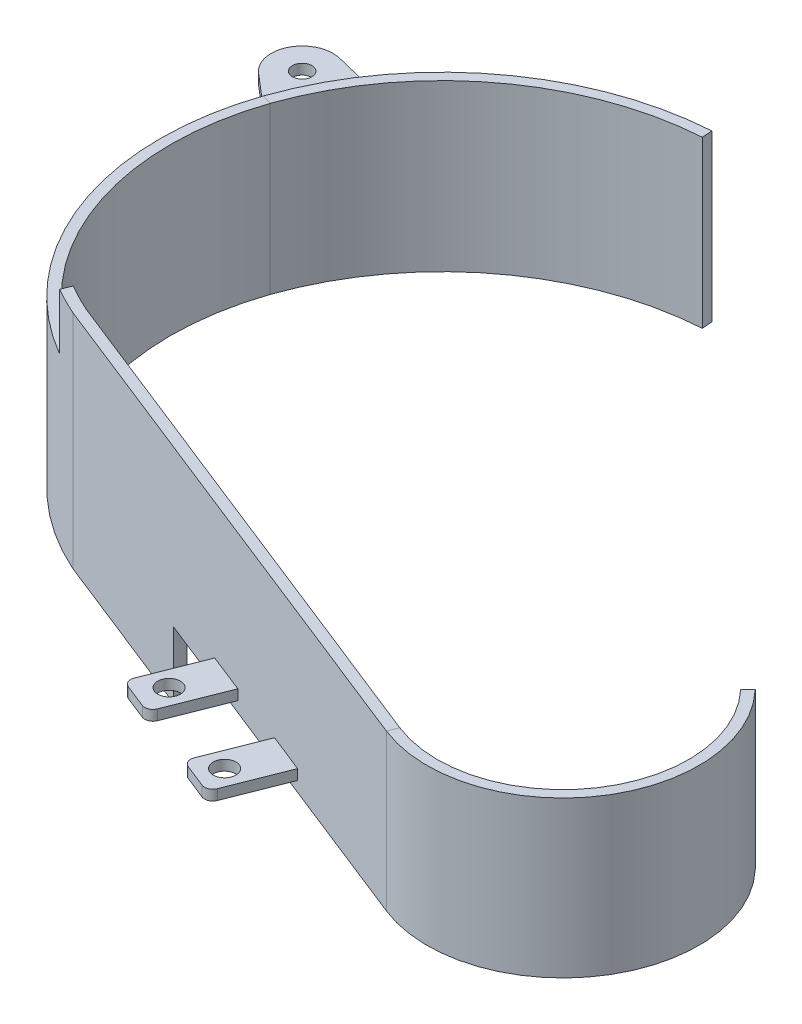
SolidWorks part; units mm, degrees
material "Alloy Steel"
ref_plane "X-Y Datum" through (0, 0, 0) normal (0, 0, 1) x (1, 0, 0)
ref_plane "X-Z Datum" through (0, 0, 0) normal (0, 1, 0) x (1, 0, 0)
ref_plane "Y-Z Datum" through (0, 0, 0) normal (1, 0, 0) x (0, 0, -1)
sketch "Sketch1" plane through (0, 0, 0) normal (0, 1, 0) x (1, 0, 0)
  line L0 (123.382, -46.1795) -> (82.7282, 60.9521) construction
  line L5 (80.7697, -109.5243) -> (-79.1962, -46.1795)
  line L6 (79.6008, -112.4763) -> (-80.422, -49.109)
  line L7 (123.0779, -46.7799) -> (125.3764, -44.5896)
  line L8 (-47.6198, 112.0697) -> (-47.8229, 115.2382)
  circle A0 centre (-42.1273, 26.3928) radius 85.8527 construction
  circle A1 centre (95.0328, -73.5055) radius 38.74 construction
  circle A2 centre (-7.1811, -92.7179) radius 3.5 construction
  circle A3 centre (22.9767, -105.7566) radius 3.5 construction
  circle A4 centre (-130.7728, 71.8939) radius 3 construction
  circle A5 centre (112.1618, -33.1147) radius 3.3 construction
  arc A6 (123.0779, -46.7799) -> (80.7697, -109.5243) centre (95.0328, -73.5055) cw
  arc A12 (-79.1962, -46.1795) -> (-123.2617, 54.4625) centre (-46.352, 28.169) cw
  arc A13 (-47.8229, 115.2382) -> (-126.2641, 55.4951) centre (-42.1273, 26.3928) ccw
  arc A14 (-80.422, -49.109) -> (-126.2641, 55.4951) centre (-46.352, 28.169) cw
  arc A15 (125.3764, -44.5896) -> (79.6008, -112.4763) centre (95.0328, -73.5055) cw
  arc A16 (-47.6198, 112.0697) -> (-123.2617, 54.4625) centre (-42.1273, 26.3928) ccw
  point P21 (-81.3964, -41.8997)
  point P34 (-78.7078, -46.7799)
  point P35 (-79.5053, -46.7799)
  point P37 (-79.1962, -46.7799)
  dimension "D1" = 6
  dimension "D2" = 171.7054
  dimension "D3" = 6.6
  dimension "D4" = 77.48
  dimension "D5" = 7
  dimension "D22" = 3.175
  dimension "D23" = 17.4234
  dimension "D6" = 22.9767
  dimension "D7" = 82.7282
  dimension "D8" = 95.0328
  dimension "D9" = 112.1618
  dimension "D10" = 123.382
  dimension "D11" = 7.1811
  dimension "D12" = 42.1273
  dimension "D13" = 130.7728
  dimension "D14" = 26.3928
  dimension "D15" = 60.9521
  dimension "D16" = 71.8939
  dimension "D17" = 33.1147
  dimension "D18" = 46.1795
  dimension "D19" = 73.5055
  dimension "D20" = 92.7179
  dimension "D21" = 105.7566
  dimension "D27" = 85.5529
  dimension "D28" = 17.4314
base flange "Base-Flange2" sketch "Sketch1" thickness 63.5 reverse thickness direction no parameters "D1"=0.7366
sketch "Sketch8" plane through (-27.712, 0, 69.9816) normal (-0.3682, 0, 0.9298) x (0.9298, 0, 0.3682)
  line L0 (36.9674, 0) -> (-134.738, 0) construction
  line L1 (-152.1442, -15.4686) -> (179.8218, -15.4686)
  line L2 (-152.1442, -15.4686) -> (-152.1442, 15.4686)
  line L3 (-152.1442, 15.4686) -> (179.8218, 15.4686)
  line L4 (179.8218, -15.4686) -> (179.8218, 15.4686)
  line L5 (-152.1442, -15.4686) -> (179.8218, 15.4686) construction
  line L6 (-152.1442, 15.4686) -> (179.8218, -15.4686) construction
  point P0 (13.8388, 0)
  dimension "D1" = 30.9372
extrude "Cut-Extrude1" cut sketch "Sketch8" against normal through all contours L2 L1 L4 L3 normal cut yes
sketch "Sketch9" plane through (-27.712, 0, 69.9816) normal (-0.3682, 0, 0.9298) x (0.9298, 0, 0.3682)
  line L0 (-56.6923, -15.4686) -> (-137.8267, -15.4686) construction
  line L1 (-215.9911, -32.8081) -> (-65.9363, -32.8081)
  line L2 (-215.9911, -32.8081) -> (-215.9911, 1.8709)
  line L3 (-215.9911, 1.8709) -> (-65.9363, 1.8709)
  line L4 (-65.9363, -32.8081) -> (-65.9363, 1.8709)
  line L5 (-215.9911, -32.8081) -> (-65.9363, 1.8709) construction
  line L6 (-215.9911, 1.8709) -> (-65.9363, -32.8081) construction
  point P0 (-140.9637, -15.4686)
  dimension "D1" = 34.679
extrude "Cut-Extrude2" cut sketch "Sketch9" against normal through all normal cut yes
sketch "Sketch11" plane through (0, -63.5, 0) normal (0, -1, 0) x (1, 0, 0)
  line L0 (-47.6198, -112.0697) -> (-47.8229, -115.2382) construction
  line L1 (-47.6198, -112.0697) -> (-47.8229, -115.2382)
  line L3 (-80.422, 49.109) -> (-29.0097, 69.4677)
  line L4 (-80.422, 49.109) -> (79.6008, 112.4763) construction
  line L5 (-29.0097, 69.4677) -> (-27.8408, 66.5157)
  line L6 (80.7697, 109.5243) -> (-79.1962, 46.1795) construction
  line L7 (-27.8408, 66.5157) -> (-79.1962, 46.1795)
  arc A0 (-79.1962, 46.1795) -> (-123.2617, -54.4625) centre (-46.352, -28.169) ccw construction
  arc A1 (-80.422, 49.109) -> (-126.2641, -55.4951) centre (-46.352, -28.169) ccw construction
  arc A2 (-126.2641, -55.4951) -> (-47.8229, -115.2382) centre (-42.1273, -26.3928) ccw construction
  arc A3 (-123.2617, -54.4625) -> (-47.6198, -112.0697) centre (-42.1273, -26.3928) ccw construction
  arc A4 (-79.1962, 46.1795) -> (-123.2617, -54.4625) centre (-46.352, -28.169) ccw
  arc A5 (-80.422, 49.109) -> (-126.2641, -55.4951) centre (-46.352, -28.169) ccw
  arc A6 (-126.2641, -55.4951) -> (-47.8229, -115.2382) centre (-42.1273, -26.3928) ccw
  arc A7 (-123.2617, -54.4625) -> (-47.6198, -112.0697) centre (-42.1273, -26.3928) ccw
  point P7 (-27.8408, 69.4677)
extrude "Boss-Extrude1" add sketch "Sketch11" along normal blind 20.32 contours A4 A7 L1 A6 A5 L3 L5 L7
sketch "Sketch12" plane through (-27.712, 0, 69.9816) normal (-0.3682, 0, 0.9298) x (0.9298, 0, 0.3682)
  line L0 (60.2996, -15.4686) -> (60.2996, -50015.4686) construction
  line L3 (27.4596, -15.4686) -> (27.4596, -50015.4686) construction
  line L6 (27.4596, -63.5) -> (60.2996, -63.5) construction
  line L11 (21.1096, -60.2996) -> (33.8096, -60.2996)
  line L12 (21.1096, -60.2996) -> (21.1096, -57.1246)
  line L13 (21.1096, -57.1246) -> (33.8096, -57.1246)
  line L14 (33.8096, -60.2996) -> (33.8096, -57.1246)
  line L15 (21.1096, -60.2996) -> (33.8096, -57.1246) construction
  line L16 (21.1096, -57.1246) -> (33.8096, -60.2996) construction
  line L17 (-1.3958, -63.5) -> (115.4202, -63.5) construction
  line L18 (43.8796, -63.5) -> (43.8796, -15.4686) construction
  line L19 (-56.6923, -15.4686) -> (115.4202, -15.4686) construction
  line L20 (66.6496, -57.1246) -> (53.9496, -57.1246)
  line L21 (53.9496, -60.2996) -> (53.9496, -57.1246)
  line L22 (66.6496, -60.2996) -> (53.9496, -60.2996)
  line L23 (66.6496, -60.2996) -> (66.6496, -57.1246)
  circle A0 centre (27.4596, -58.7121) radius 3.3 construction
  point P4 (27.4596, -52.269)
  dimension "D1" = 6.6
  dimension "D2" = 3.2004
  dimension "D3" = 3.175
  dimension "D4" = 12.7
extrude "Boss-Extrude2" add sketch "Sketch12" along normal blind 21.59
sketch "Sketch13" plane through (0, -57.1246, 0) normal (0, 1, 0) x (1, 0, 0)
  circle A0 centre (22.9767, -105.7566) radius 3.5 construction
  circle A1 centre (-7.1811, -92.7179) radius 3.5 construction
  circle A2 centre (22.9767, -105.7566) radius 3.5
  circle A3 centre (-7.1811, -92.7179) radius 3.5
extrude "Cut-Extrude5" cut sketch "Sketch13" against normal blind 21.59 normal cut yes
fillet "Fillet1" radius 2.54 4 edges at (-16.034, -58.7121, 97.8271) (-4.2261, -58.7121, 102.5029) (14.4992, -58.7121, 109.9179) (26.3071, -58.7121, 114.5937)
ref_plane "Plane1" through (0, -36.6727, 0) normal (0, 1, 0) x (1, 0, 0)
sketch "Sketch14" plane through (0, -36.6727, 0) normal (0, 1, 0) x (1, 0, 0)
  line L0 (-136.9673, 64.6583) -> (-126.2641, 55.4951)
  line L2 (-130.7728, 71.8939) -> (-121.3305, 67.0473) construction
  line L3 (-128.5048, 81.145) -> (-114.8202, 77.7901)
  circle A0 centre (-130.7728, 71.8939) radius 3 construction
  circle A1 centre (-130.7728, 71.8939) radius 3
  circle A2 centre (-130.7728, 71.8939) radius 9.525 construction
  arc A3 (-47.8229, 115.2382) -> (-126.2641, 55.4951) centre (-42.1273, 26.3928) ccw construction
  arc A4 (-47.8229, 115.2382) -> (-126.2641, 55.4951) centre (-42.1273, 26.3928) ccw construction
  arc A5 (-126.2641, 55.4951) -> (-114.8202, 77.7901) centre (-42.1273, 26.3928) cw
  arc A6 (-128.5048, 81.145) -> (-136.9673, 64.6583) centre (-130.7728, 71.8939) ccw
  dimension "D1" = 19.05
extrude "Boss-Extrude3" add sketch "Sketch14" against normal blind 3.175
sketch "Bend-Lines1" [suppressed] plane through (0, 0, 0) normal (0, 1, 0) x (1, 0, 0)
sketch "Bounding-Box1" [suppressed] plane through (0, 0, 0) normal (0, 1, 0) x (1, 0, 0)
sheet metal parameters "Sheet-Metal2" thickness 63.5 parameters "D1"=0.7366
flat pattern "Flat-Pattern2" [suppressed]
sketch "Bend-Lines3" plane through (0, 0, 0) normal (0, 1, 0) x (1, 0, 0)
sketch3d "Bounding-Box3" [suppressed]
  line L0 (59.1704, 2.3147, 0) -> (-160.9269, 205.4198, 0) construction
  line L1 (-40.4074, -105.5941, 0) -> (-260.5047, 97.5111, 0) construction
  line L2 (59.1704, 2.3147, 0) -> (-40.4074, -105.5941, 0) construction
  line L3 (-160.9269, 205.4198, 0) -> (-260.5047, 97.5111, 0) construction
sheet metal parameters "Sheet-Metal3" thickness 63.5 parameters "D1"=0.7366
flat pattern "Flat-Pattern2"
sketch "Bend-Lines3" plane through (0, 0, 0) normal (0, 1, 0) x (1, 0, 0)
sketch3d "Bounding-Box3" [suppressed]
  line L0 (-59.1704, 2.3147, 0) -> (160.9269, 205.4198, 0) construction
  line L1 (40.4074, -105.5941, 0) -> (260.5047, 97.5111, 0) construction
  line L2 (-59.1704, 2.3147, 0) -> (40.4074, -105.5941, 0) construction
  line L3 (160.9269, 205.4198, 0) -> (260.5047, 97.5111, 0) construction
sheet metal parameters "Sheet-Metal4" thickness 63.5 parameters "D1"=0.7366
flat pattern "Flat-Pattern2"
sketch "Bend-Lines3" plane through (0, 0, 0) normal (0, 1, 0) x (1, 0, 0)
sketch3d "Bounding-Box3" [suppressed]
  line L0 (-59.1764, 2.3234, 0) -> (160.9292, 205.4207, 0) construction
  line L1 (40.8138, -106.0404, 0) -> (260.9194, 97.0569, 0) construction
  line L2 (-59.1764, 2.3234, 0) -> (40.8138, -106.0404, 0) construction
  line L3 (160.9292, 205.4207, 0) -> (260.9194, 97.0569, 0) construction
sheet metal parameters "Sheet-Metal7" thickness 63.5 parameters "D1"=0.7366
flat pattern "Flat-Pattern2"
sketch "Bend-Lines3" plane through (0, 0, 0) normal (0, 1, 0) x (1, 0, 0)
sketch3d "Bounding-Box3" [suppressed]
  line L0 (137.4426, 12.0381, 0) -> (-39.1246, 29.8168, 0) construction
  line L1 (130.6639, -55.2836, 0) -> (-45.9033, -37.5049, 0) construction
  line L2 (137.4426, 12.0381, 0) -> (130.6639, -55.2836, 0) construction
  line L3 (-39.1246, 29.8168, 0) -> (-45.9033, -37.5049, 0) construction
sheet metal parameters "Sheet-Metal8" thickness 63.5 parameters "D1"=0.7366
flat pattern "Flat-Pattern2"
sketch "Bend-Lines3" plane through (0, 0, 0) normal (0, 1, 0) x (1, 0, 0)
sketch3d "Bounding-Box3" [suppressed]
  line L0 (137.4426, 12.0381, 0) -> (-39.1246, 29.8168, 0) construction
  line L1 (130.6639, -55.2836, 0) -> (-45.9033, -37.5049, 0) construction
  line L2 (137.4426, 12.0381, 0) -> (130.6639, -55.2836, 0) construction
  line L3 (-39.1246, 29.8168, 0) -> (-45.9033, -37.5049, 0) construction
sheet metal parameters "Sheet-Metal9" thickness 63.5 parameters "D1"=0.7366
flat pattern "Flat-Pattern2"
sketch "Bend-Lines3" plane through (0, 0, 0) normal (0, 1, 0) x (1, 0, 0)
sketch3d "Bounding-Box3" [suppressed]
  line L0 (137.4426, 12.0381, 0) -> (-39.1246, 29.8168, 0) construction
  line L1 (130.6639, -55.2836, 0) -> (-45.9033, -37.5049, 0) construction
  line L2 (137.4426, 12.0381, 0) -> (130.6639, -55.2836, 0) construction
  line L3 (-39.1246, 29.8168, 0) -> (-45.9033, -37.5049, 0) construction
sheet metal parameters "Sheet-Metal10" thickness 63.5 parameters "D1"=0.7366
flat pattern "Flat-Pattern2"
sketch "Bend-Lines3" plane through (0, 0, 0) normal (0, 1, 0) x (1, 0, 0)
sketch3d "Bounding-Box3" [suppressed]
  line L0 (124.433, 6.7667, 0) -> (-38.0463, 30.0182, 0) construction
  line L1 (115.0493, -58.8061, 0) -> (-47.43, -35.5545, 0) construction
  line L2 (124.433, 6.7667, 0) -> (115.0493, -58.8061, 0) construction
  line L3 (-38.0463, 30.0182, 0) -> (-47.43, -35.5545, 0) construction
